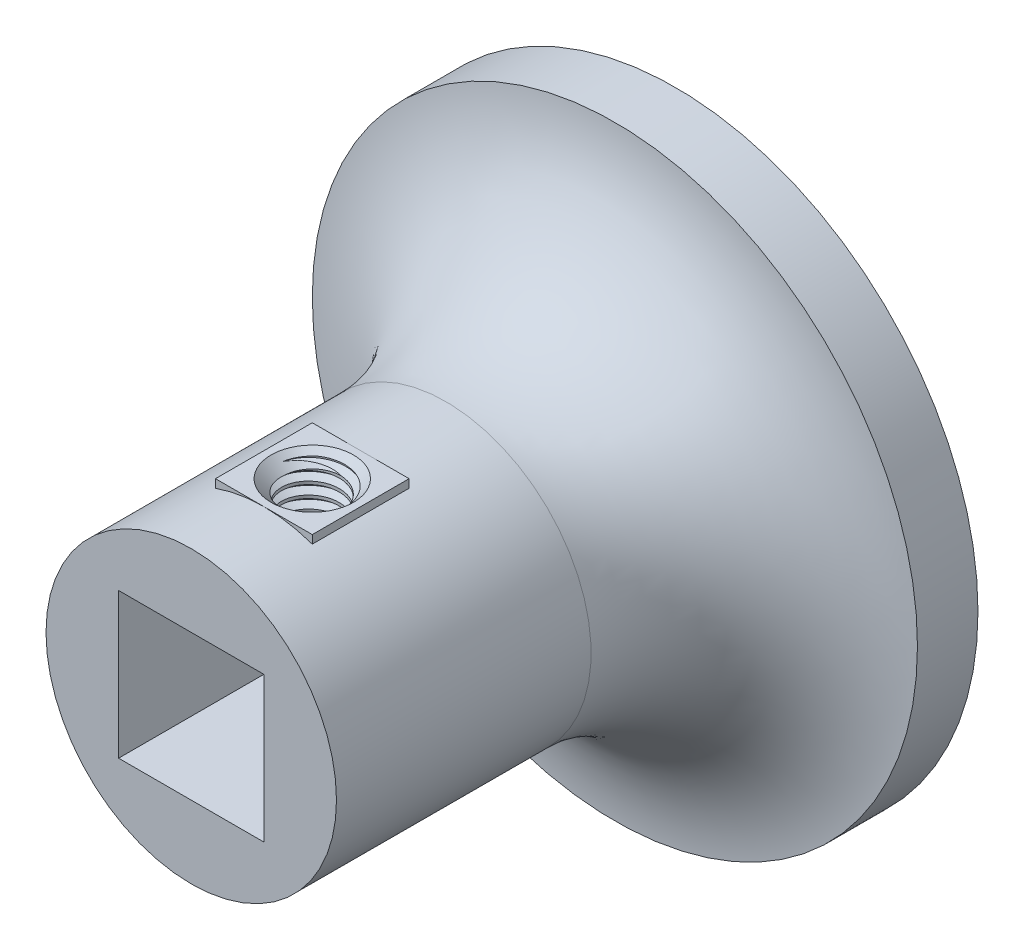
SolidWorks part; units mm, degrees
ref_plane "Front Plane" through (0, 0, 0) normal (0, 0, 1) x (1, 0, 0)
ref_plane "Top Plane" through (0, 0, 0) normal (0, 1, 0) x (1, 0, 0)
ref_plane "Right Plane" through (0, 0, 0) normal (1, 0, 0) x (0, 0, -1)
sketch "Sketch1" plane through (0, 0, 0) normal (0, 0, 1) x (1, 0, 0)
  circle A0 centre (0, 0) radius 12.5
  dimension "D1" = 25
extrude "Boss-Extrude1" add sketch "Sketch1" along normal blind 3
sketch "Sketch4" plane through (0, 0, 0) normal (0, 0, -1) x (-1, 0, 0)
  circle A0 centre (0, 0) radius 3.505
  dimension "D1" = 7.01
extrude "Cut-Extrude1" cut sketch "Sketch4" against normal blind 2.5
sketch "Sketch5" plane through (0, 0, 3) normal (0, 0, 1) x (1, 0, 0)
  circle A0 centre (0, 0) radius 6
  dimension "D1" = 12
extrude "Boss-Extrude2" add sketch "Sketch5" along normal blind 17.5
sketch "Sketch6" plane through (0, 0, 2.5) normal (0, 0, -1) x (-1, 0, 0)
  circle A0 centre (0, 0) radius 2.005
  dimension "D1" = 4.01
extrude "Cut-Extrude2" cut sketch "Sketch6" against normal blind 1.5
sketch "Sketch7" plane through (0, 0, 4) normal (0, 0, -1) x (-1, 0, 0)
  line L0 (-1.3248, 1.505) -> (1.3248, 1.505)
  line L1 (-2.3292, -2.005) -> (3.8039, -2.005) construction
  arc A0 (-1.3248, 1.505) -> (1.3248, 1.505) centre (0, 0) ccw
  dimension "D1" = 4.01
  dimension "D2" = 3.51
extrude "Cut-Extrude3" cut sketch "Sketch7" against normal blind 8
fillet "Fillet1" radius 7 1 edges at (6, 0, 3)
sketch "Sketch8" plane through (0, 0, 20.5) normal (0, 0, 1) x (1, 0, 0)
  line L0 (-3, 3) -> (3, 3)
  line L1 (3, 3) -> (3, -3)
  line L2 (3, -3) -> (-3, -3)
  line L3 (-3, -3) -> (-3, 3)
  line L4 (-11.7665, 0) -> (10.1735, 0) construction
  line L5 (0, 5.5424) -> (0, -5.1799) construction
  dimension "D1" = 6
  dimension "D2" = 6
extrude "Cut-Extrude4" cut sketch "Sketch8" against normal up to surface (8.5 mm away) up to face at (0, -0.25, 12)
ref_plane "Plane1" through (0, 6, 0) normal (0, 1, 0) x (1, 0, 0)
sketch "Sketch23" plane through (0, 6, 0) normal (0, 1, 0) x (1, 0, 0)
  line L0 (-6, -20.5) -> (6, -20.5) construction
  line L1 (-2, -13.5) -> (2, -13.5)
  line L2 (-2, -13.5) -> (-2, -17.5)
  line L3 (-2, -17.5) -> (2, -17.5)
  line L4 (2, -13.5) -> (2, -17.5)
  line L5 (-2, -13.5) -> (2, -17.5) construction
  line L6 (-2, -17.5) -> (2, -13.5) construction
  point P0 (0, -15.5)
  dimension "D1" = 4
  dimension "D2" = 4
  dimension "D3" = 5
extrude "Boss-Extrude3" add sketch "Sketch23" against normal up to surface (0.3431 mm away) up to face at (-6, 0, 9.9821)
sketch "Sketch24" plane through (0, 6, 0) normal (0, 1, 0) x (1, 0, 0)
  line L1 (2, -17.5) -> (2, -13.5) construction
  circle A0 centre (0, -15.5) radius 1.2
  dimension "D1" = 2.4
  dimension "D2" = 2
  dimension "D3" = 2
extrude "Cut-Extrude6" cut sketch "Sketch24" against normal blind 7
chamfer "Chamfer3" distance 0.5 angle 45 1 edges at (0, 6, 16.7)
thread "Thread3" pitch 0.5 method cut trim with start face yes profile "Thread Profile3" start angle 0, offset 1, length 5, pitch 0.5, diameter 2.4
ref_plane "Plane4" through (-1.2, 6.5, 15.5) normal (0, 0, 1) x (-1, 0, 0)
sketch "Thread Profile3" plane through (-1.2, 6.5, 15.5) normal (0, 0, 1) x (-1, 0, 0)
  line L0 (0, 0) -> (0, 0.5) construction
  line L1 (0, 0) -> (0.2706, 0.1562)
  line L2 (0.2706, 0.1562) -> (0.2706, 0.2187)
  line L3 (0.2706, 0.2187) -> (0, 0.375)
  line L4 (0.2706, 0.1875) -> (0, 0.1875) construction
  line L11 (0, 0) -> (0, 0.375)
  point P2 (0, 0)
  dimension "Pitch" = 0.5
  dimension "Profile_Angle" = 60
  dimension "Profile_Land" = 0.0625
  dimension "Profile_Height" = 0.2706
sketch "Sketch25" plane through (0, 0, 0) normal (0, 0, -1) x (-1, 0, 0)
  circle A0 centre (0, 0) radius 12.775
  circle A1 centre (0, 0) radius 3.505
extrude "Cut-Extrude9" cut sketch "Sketch25" against normal blind 0.5
